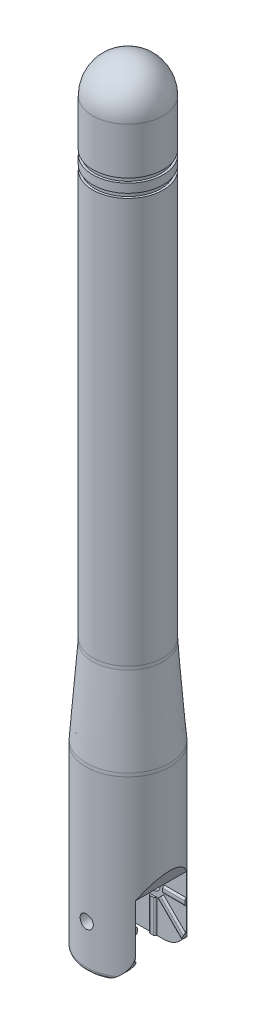
SolidWorks part; units mm, degrees
ref_plane "Plan de face" through (0, 0, 0) normal (0, 0, 1) x (1, 0, 0)
ref_plane "Plan de dessus" through (0, 0, 0) normal (0, 1, 0) x (1, 0, 0)
ref_plane "Plan de droite" through (0, 0, 0) normal (1, 0, 0) x (0, 0, -1)
sketch "Esquisse2" plane through (0, 0, 0) normal (0, 0, 1) x (1, 0, 0)
  line L0 (0, 0) -> (0, 87.9508) construction
  line L1 (0, 87.9508) -> (4, 87.9508) construction
  line L2 (4, 87.9508) -> (4, 0) construction
  line L3 (4, 0) -> (0, 0) construction
  line L4 (4, 0) -> (4.75, 0) construction
  line L5 (4.75, 0) -> (4.75, 20.4) construction
  line L6 (4.75, 20.4) -> (0, 20.4) construction
  line L7 (4, 83.9508) -> (4, 30.5872) construction
  line L8 (4.014, 30.2133) -> (4.736, 20.5867)
  line L9 (4.75, 20.2128) -> (4.75, 0)
  line L10 (4.75, 0) -> (1, 0)
  line L11 (1, 0) -> (1, 83.9508)
  line L12 (1, 83.9508) -> (0, 83.9508)
  line L13 (4, 83.9508) -> (4, 78.6508)
  line L14 (4, 78.6508) -> (3.75, 78.6508)
  line L15 (3.75, 78.6508) -> (3.75, 78.1508)
  line L16 (3.75, 78.1508) -> (4, 78.1508)
  line L17 (4, 78.1508) -> (4, 77.1508)
  line L18 (4, 77.1508) -> (3.75, 77.1508)
  line L19 (3.75, 77.1508) -> (3.75, 76.6508)
  line L20 (3.75, 76.6508) -> (4, 76.6508)
  line L21 (0, 87.9508) -> (0, 83.9508)
  line L22 (4, 76.6508) -> (4, 30.5872)
  arc A0 (0, 87.9508) -> (4, 83.9508) centre (0, 83.9508) cw
  arc A1 (4.75, 20.2128) -> (4.736, 20.5867) centre (-0.25, 20.2128) ccw
  arc A2 (4.014, 30.2133) -> (4, 30.5872) centre (9, 30.5872) cw
  point P18 (4, 30.4)
  point P25 (3.875, 77.1508)
  dimension "D7" = 5
  dimension "D1" = 87.9508
  dimension "D2" = 8
  dimension "D3" = 9.5
  dimension "D4" = 20.4
  dimension "D5" = 2
  dimension "D6" = 10
  dimension "D8" = 9.3
  dimension "D9" = 0.5
  dimension "D10" = 1.5
  dimension "D11" = 7.5
revolve "Révolution1" add sketch "Esquisse2" angle 360 about L0
sketch "Esquisse3" plane through (0, 0, 0) normal (0, -1, 0) x (1, 0, 0)
  line L0 (0, 0) -> (-2.75, 0) construction
  line L1 (-2.75, 2.9) -> (4.75, 2.9)
  line L2 (-2.75, 2.9) -> (-2.75, -2.9)
  line L3 (-2.75, -2.9) -> (4.75, -2.9)
  line L4 (4.75, 2.9) -> (4.75, -2.9)
  line L5 (-4.75, 0) -> (-2.75, 0) construction
  circle A0 centre (0, 0) radius 4.75 construction
  dimension "D1" = 5.8
  dimension "D2" = 2
extrude "Enlèv. mat.-Extru.1" cut sketch "Esquisse3" against normal blind 8
fillet "Congé1" radius 0.5 1 edges at (-4.75, 0, 0)
sketch "Esquisse4" plane through (0, 0, 0) normal (0, 0, 1) x (1, 0, 0)
  line L0 (3.762, 8) -> (3.762, 0.5) construction
  line L1 (-4.75, 0) -> (3.762, 0) construction
  line L2 (1.162, 0) -> (3.762, 0)
  line L3 (3.762, 0) -> (3.762, 2.6)
  line L4 (0, 0) -> (0, 5) construction
  line L5 (3.762, 8) -> (4.75, 10)
  line L6 (4.75, 8) -> (4.75, 20.2128) construction
  line L7 (4.75, 10) -> (4.75, 8)
  line L8 (3.762, 8) -> (4.75, 8) construction
  line L9 (4.75, 8) -> (3.762, 8)
  arc A0 (3.762, 2.6) -> (1.162, 0) centre (1.162, 2.6) cw
  circle A1 centre (0, 5) radius 0.75
  dimension "D1" = 2.6
  dimension "D3" = 1.5
  dimension "D2" = 5
  dimension "D4" = 2
extrude "Enlèv. mat.-Extru.2" cut sketch "Esquisse4" against normal through all both and the other way through all
sketch "Esquisse5" plane through (0, 0, -2.9) normal (0, 0, 1) x (1, 0, 0)
  line L0 (-4.25, 0) -> (1.162, 0) construction
  line L1 (-0.375, 0) -> (0.375, 0)
  line L2 (-0.375, 0) -> (-0.375, 3.75)
  line L3 (-0.375, 3.75) -> (0.375, 3.75)
  line L4 (0.375, 0) -> (0.375, 3.75)
  line L5 (0, 5) -> (0, 3.75) construction
  line L6 (0, 5) -> (3.762, 1.238) construction
  line L7 (3.762, 8) -> (3.762, 2.6) construction
  line L8 (0.6187, 3.851) -> (3.4968, 0.9729) construction
  line L9 (0.6187, 3.851) -> (1.149, 4.3813)
  line L10 (3.4968, 0.9729) -> (4.0271, 1.5032)
  line L11 (1.149, 4.3813) -> (4.0271, 1.5032) construction
  line L12 (0.6187, 3.851) -> (4.0271, 1.5032) construction
  line L13 (3.4968, 0.9729) -> (1.149, 4.3813) construction
  line L14 (1.149, 4.3813) -> (4.0271, 1.5032)
  line L15 (0.6187, 3.851) -> (3.4968, 0.9729)
  line L16 (0, 5) -> (3.762, 5) construction
  line L18 (1.25, 4.625) -> (3.762, 4.625)
  line L19 (1.25, 4.625) -> (1.25, 5.375)
  line L20 (1.25, 5.375) -> (3.762, 5.375)
  line L21 (3.762, 4.625) -> (3.762, 5.375)
  line L22 (1.25, 4.625) -> (3.762, 5.375) construction
  line L23 (1.25, 5.375) -> (3.762, 4.625) construction
  point P13 (2.3229, 2.6771)
  point P18 (2.506, 5)
  dimension "D1" = 0.75
  dimension "D2" = 1.25
  dimension "D3" = 45
  dimension "D4" = 1.25
  dimension "D5" = 1.25
extrude "Boss.-Extru.1" add sketch "Esquisse5" along normal blind 0.2
fillet "Congé2" radius 0.2 6 edges at (2.506, 5.375, -2.7) (2.506, 4.625, -2.7) (2.5881, 2.9422, -2.7) (2.0578, 2.4119, -2.7) (-0.375, 1.875, -2.7) (0.375, 1.875, -2.7)
mirror "Symétrie1" about plane through (0, 0, 0) normal (0, 0, 1) of "Congé2", "Boss.-Extru.1"
sketch "Esquisse6" plane through (0, 0, 2.9) normal (0, 0, 1) x (1, 0, 0)
  line L3 (4.0271, 1.5032) -> (3.6581, 1.8723)
  line L4 (3.3199, 1.1497) -> (3.4968, 0.9729)
  line L5 (3.4968, 0.9729) -> (4.0271, 1.5032)
  line L6 (4.0271, 1.5032) -> (3.6581, 1.8723)
  line L7 (3.3199, 1.1497) -> (3.4968, 0.9729)
  line L8 (3.4968, 0.9729) -> (4.0271, 1.5032)
  arc A1 (3.3199, 1.1497) -> (3.6581, 1.8723) centre (1.162, 2.6) ccw
  arc A2 (3.3199, 1.1497) -> (3.6581, 1.8723) centre (1.162, 2.6) ccw
  dimension "D1" = 0
extrude "Enlèv. mat.-Extru.3" cut sketch "Esquisse6" against normal through all
